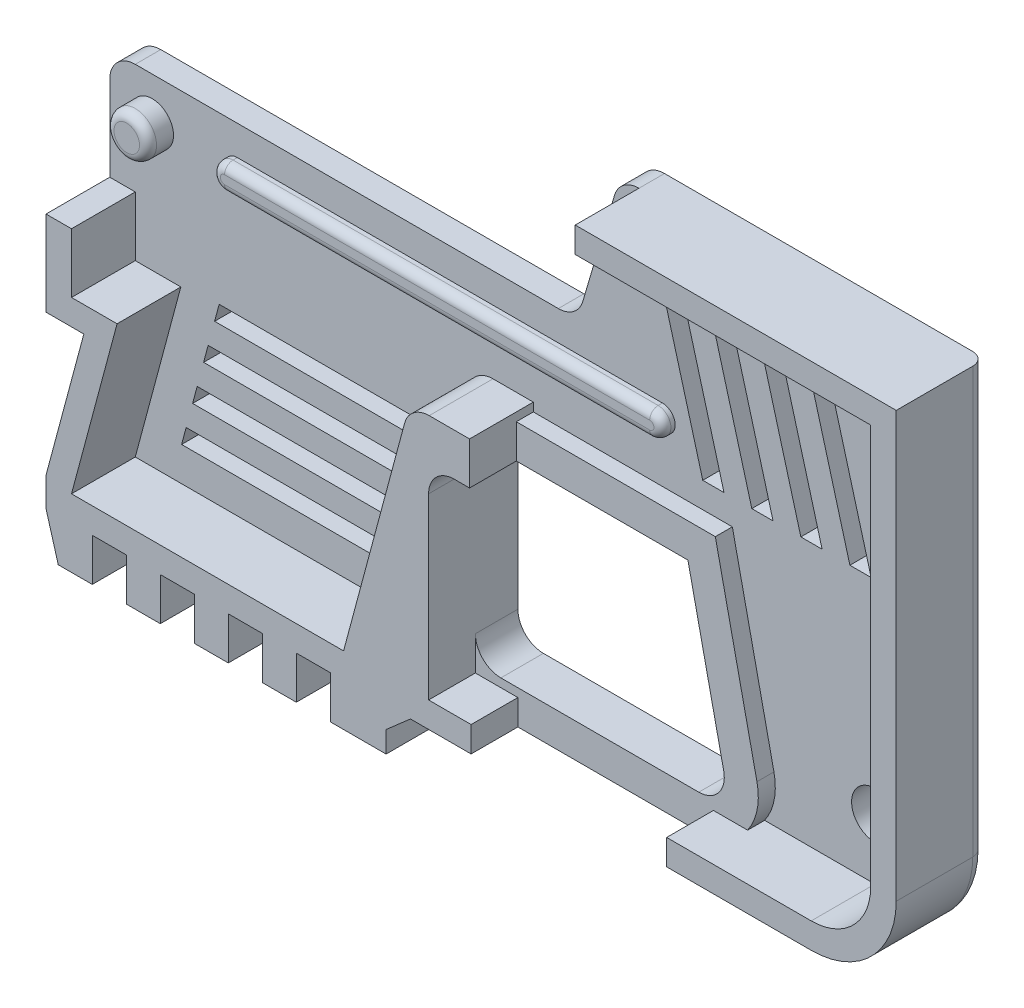
SolidWorks part; units mm, degrees
ref_plane "Front Plane" through (0, 0, 0) normal (0, 0, 1) x (1, 0, 0)
ref_plane "Top Plane" through (0, 0, 0) normal (0, 1, 0) x (1, 0, 0)
ref_plane "Right Plane" through (0, 0, 0) normal (1, 0, 0) x (0, 0, -1)
sketch "Sketch1" plane through (0, 0, 0) normal (0, 0, 1) x (1, 0, 0)
  line L0 (0.6334, 2.1535) -> (4.3666, 14.8465)
  line L1 (7.2447, 17) -> (45, 17)
  line L2 (45, 17) -> (45, -33)
  line L3 (35, -43) -> (-55, -43)
  line L4 (-55, -43) -> (-55, -3)
  line L5 (-52, 0) -> (-2.2447, 0)
  arc A0 (-55, -3) -> (-52, 0) centre (-52, -3) cw
  arc A1 (4.3666, 14.8465) -> (7.2447, 17) centre (7.2447, 14) cw
  arc A2 (0.6334, 2.1535) -> (-2.2447, 0) centre (-2.2447, 3) cw
  arc A3 (45, -33) -> (35, -43) centre (35, -33) cw
  point P9 (-55, 0)
  point P12 (5, 17)
  point P15 (0, 0)
  point P18 (45, -43)
  dimension "D6" = 3
  dimension "D7" = 3
  dimension "D8" = 10
  dimension "D1" = 100
  dimension "D2" = 60
  dimension "D3" = 17
  dimension "D4" = 40
  dimension "D5" = 55
extrude "Boss-Extrude1" add sketch "Sketch1" along normal blind 3
sketch "Sketch2" plane through (0, 0, 3) normal (0, 0, 1) x (1, 0, 0)
  line L0 (-7, -16) -> (15, -16)
  line L1 (15, -16) -> (19.2093, -35.3627)
  line L2 (16.2778, -39) -> (-7, -39)
  line L3 (-10, -36) -> (-10, -19)
  line L4 (-55, -43) -> (35, -43) construction
  line L5 (45, -33) -> (45, 17) construction
  arc A0 (19.2093, -35.3627) -> (16.2778, -39) centre (16.2778, -36) cw
  arc A1 (-7, -39) -> (-10, -36) centre (-7, -36) cw
  arc A2 (-7, -16) -> (-10, -19) centre (-7, -19) ccw
  point P8 (0, 0)
  point P11 (20, -39)
  point P14 (-10, -39)
  point P17 (-10, -16)
  dimension "D6" = 3
  dimension "D1" = 4
  dimension "D2" = 23
  dimension "D3" = 30
  dimension "D4" = 25
  dimension "D5" = 25
extrude "Cut-Extrude1" cut sketch "Sketch2" against normal through all
sketch "Sketch3" plane through (0, 0, 3) normal (0, 0, 1) x (1, 0, 0)
  line L0 (45, -33) -> (45, 17) construction
  line L1 (45, 17) -> (7.2447, 17) construction
  line L2 (45, -33) -> (45, 17)
  line L3 (45, 17) -> (7.2447, 17)
  line L4 (35, -43) -> (18, -43)
  line L5 (-55, -43) -> (35, -43) construction
  line L6 (35, -40) -> (18, -40)
  line L7 (42, -33) -> (42, 14)
  line L8 (42, 14) -> (7.2447, 14)
  line L9 (7.2447, 14) -> (7.2447, 17)
  line L10 (18, -40) -> (18, -43)
  line L11 (-5, -43) -> (-55, -43)
  line L12 (-55, -43) -> (-55, -13)
  line L13 (-55, -3) -> (-55, -43) construction
  line L14 (-55, -13) -> (-52, -13)
  line L15 (-52, -13) -> (-52, -40)
  line L16 (-52, -40) -> (-5, -40)
  line L17 (-5, -40) -> (-5, -43)
  arc A0 (35, -43) -> (45, -33) centre (35, -33) ccw construction
  arc A1 (35, -43) -> (45, -33) centre (35, -33) ccw
  arc A2 (35, -40) -> (42, -33) centre (35, -33) ccw
  dimension "D2" = 17
  dimension "D3" = 3
  dimension "D4" = 30
  dimension "D5" = 50
  dimension "D1" = 3
extrude "Boss-Extrude2" add sketch "Sketch3" along normal blind 7.5
sketch "Sketch4" plane through (0, 0, 3) normal (0, 0, 1) x (1, 0, 0)
  line L0 (15, -16) -> (-7, -16) construction
  line L1 (-10, -19) -> (-10, -36) construction
  line L2 (-7, -39) -> (16.2778, -39) construction
  line L3 (19.2093, -35.3627) -> (15, -16) construction
  line L4 (15, -16) -> (-7, -16)
  line L5 (-10, -19) -> (-10, -36)
  line L6 (-7, -39) -> (16.2778, -39)
  line L7 (19.2093, -35.3627) -> (15, -16)
  line L8 (18.2239, -12) -> (-7, -12)
  line L9 (-14, -19) -> (-14, -36)
  line L10 (-7, -43) -> (16.2778, -43)
  line L11 (23.118, -34.513) -> (18.2239, -12)
  arc A0 (-7, -16) -> (-10, -19) centre (-7, -19) ccw construction
  arc A1 (-10, -36) -> (-7, -39) centre (-7, -36) ccw construction
  arc A2 (16.2778, -39) -> (19.2093, -35.3627) centre (16.2778, -36) ccw construction
  arc A3 (-7, -16) -> (-10, -19) centre (-7, -19) ccw
  arc A4 (-10, -36) -> (-7, -39) centre (-7, -36) ccw
  arc A5 (16.2778, -39) -> (19.2093, -35.3627) centre (16.2778, -36) ccw
  arc A6 (-7, -12) -> (-14, -19) centre (-7, -19) ccw
  arc A7 (-14, -36) -> (-7, -43) centre (-7, -36) ccw
  arc A8 (16.2778, -43) -> (23.118, -34.513) centre (16.2778, -36) ccw
  dimension "D1" = 4
extrude "Boss-Extrude3" add sketch "Sketch4" along normal blind 2
sketch "Sketch5" plane through (0, 0, 3) normal (0, 0, 1) x (1, 0, 0)
  line L0 (9.2447, 11) -> (14.7447, -9)
  line L1 (14.7447, -9) -> (17.2447, -9)
  line L2 (17.2447, -9) -> (11.7447, 11)
  line L3 (11.7447, 11) -> (9.2447, 11)
  line L4 (7.2447, 14) -> (42, 14) construction
  line L5 (23.0125, -9) -> (17.5125, 11)
  line L6 (17.5125, 11) -> (15.0125, 11)
  line L7 (15.0125, 11) -> (20.5125, -9)
  line L8 (20.5125, -9) -> (23.0125, -9)
  line L9 (28.7802, -9) -> (23.2802, 11)
  line L10 (23.2802, 11) -> (20.7802, 11)
  line L11 (20.7802, 11) -> (26.2802, -9)
  line L12 (26.2802, -9) -> (28.7802, -9)
  line L13 (34.548, -9) -> (29.048, 11)
  line L14 (29.048, 11) -> (26.548, 11)
  line L15 (26.548, 11) -> (32.048, -9)
  line L16 (32.048, -9) -> (34.548, -9)
  point P6 (34.548, -9)
  dimension "D1" = 20
  dimension "D2" = 8
  dimension "D3" = 2.5
  dimension "D4" = 3
  dimension "D5" = 2
  dimension "D6" = 4
extrude "Cut-Extrude2" cut sketch "Sketch5" against normal through all
sketch "Sketch6" plane through (0, 0, 3) normal (0, 0, 1) x (1, 0, 0)
  line L0 (-52, -40) -> (-46.641, -20)
  line L1 (-46.641, -20) -> (-52, -20)
  line L2 (-52, -40) -> (-52, -13) construction
  line L3 (-52, -20) -> (-52, -40)
  dimension "D1" = 15
  dimension "D2" = 20
extrude "Boss-Extrude4" add sketch "Sketch6" along normal blind 7.5
sketch "Sketch7" plane through (0, 0, 10.5) normal (0, 0, 1) x (1, 0, 0)
  line L2 (-55, -13) -> (-55, -43) construction
  line L3 (-55, -39.605) -> (-55, -23)
  line L4 (-54.8978, -39.2235) -> (-50.5507, -23)
  line L5 (-50.5507, -23) -> (-52, -23)
  line L6 (-55, -39.605) -> (-50.5507, -23)
  line L7 (-50.5507, -23) -> (-55, -23)
  dimension "D1" = 3
extrude "Cut-Extrude3" cut sketch "Sketch7" against normal through all
sketch "Sketch8" plane through (0, 0, 3) normal (0, 0, 1) x (1, 0, 0)
  line L0 (-10, -40) -> (-10, -19)
  line L1 (-5, -40) -> (-52, -40) construction
  line L2 (-7, -16) -> (-5.1831, -16)
  line L3 (-5.1831, -16) -> (-5.1831, -11)
  line L4 (-5.1831, -11) -> (-9.9275, -11)
  line L5 (-12.8253, -13.2235) -> (-20, -40)
  line L6 (-52, -40) -> (-46.641, -20) construction
  line L7 (15, -16) -> (-7, -16) construction
  line L8 (-20, -40) -> (-10, -40)
  arc A0 (-10, -19) -> (-7, -16) centre (-7, -19) cw
  arc A1 (-9.9275, -11) -> (-12.8253, -13.2235) centre (-9.9275, -14) ccw
  point P11 (-9.9831, -40)
  dimension "D1" = 3
  dimension "D2" = 3
  dimension "D3" = 5
  dimension "D4" = 10
extrude "Boss-Extrude5" add sketch "Sketch8" along normal blind 7.5
sketch "Sketch9" plane through (0, 0, 3) normal (0, 0, 1) x (1, 0, 0)
  line L0 (-40, -5) -> (10, -5) construction
  line L1 (-40, -3.5) -> (10, -3.5)
  line L2 (-40, -6.5) -> (10, -6.5)
  line L3 (-2.2447, 0) -> (-52, 0) construction
  line L4 (-55, -3) -> (-55, -13) construction
  arc A0 (-40, -3.5) -> (-40, -6.5) centre (-40, -5) ccw
  arc A1 (10, -6.5) -> (10, -3.5) centre (10, -5) ccw
  point P2 (-15, -5)
  point P9 (-27.1224, 0)
  dimension "D1" = 3
  dimension "D2" = 50
  dimension "D3" = 5
  dimension "D4" = 15
sketch "Sketch10" plane through (0, 0, 3) normal (0, 0, 1) x (1, 0, 0)
  line L0 (-2.2447, 0) -> (-52, 0) construction
  line L1 (-55, -3) -> (-55, -13) construction
  circle A0 centre (-50, -5) radius 2.5
  dimension "D3" = 5
  dimension "D1" = 5
  dimension "D2" = 5
extrude "Boss-Extrude6" add sketch "Sketch10" along normal blind 3
fillet "Fillet2" radius 1 1 edges at (-47.5, -5, 6)
sketch "Sketch11" plane through (0, 0, 3) normal (0, 0, 1) x (1, 0, 0)
  circle A0 centre (35, -33) radius 2.75
  dimension "D1" = 5.5
extrude "Cut-Extrude5" cut sketch "Sketch11" against normal through all
fillet "Fillet3" radius 1.5 3 edges at (-10, -43, 0) (42.0711, -40.0711, 0) (45, -8, 0)
sketch "Sketch12" plane through (0, 0, 3) normal (0, 0, 1) x (1, 0, 0)
  line L0 (-46.5517, -36) -> (-22.5517, -36)
  line L1 (-22.5517, -36) -> (-22.0158, -34)
  line L2 (-22.0158, -34) -> (-46.0158, -34)
  line L3 (-46.0158, -34) -> (-46.5517, -36)
  line L4 (-52, -40) -> (-46.641, -20) construction
  line L5 (-12.8253, -13.2235) -> (-20, -40) construction
  line L6 (-20, -40) -> (-52, -40) construction
  line L7 (-45.2576, -31.1704) -> (-21.2576, -31.1704)
  line L8 (-21.2576, -31.1704) -> (-20.7217, -29.1704)
  line L9 (-20.7217, -29.1704) -> (-44.7217, -29.1704)
  line L10 (-44.7217, -29.1704) -> (-45.2576, -31.1704)
  line L11 (-43.9635, -26.3407) -> (-19.9635, -26.3407)
  line L12 (-19.9635, -26.3407) -> (-19.4276, -24.3407)
  line L13 (-19.4276, -24.3407) -> (-43.4276, -24.3407)
  line L14 (-43.4276, -24.3407) -> (-43.9635, -26.3407)
  line L15 (-42.6694, -21.5111) -> (-18.6694, -21.5111)
  line L16 (-18.6694, -21.5111) -> (-18.1335, -19.5111)
  line L17 (-18.1335, -19.5111) -> (-42.1335, -19.5111)
  line L18 (-42.1335, -19.5111) -> (-42.6694, -21.5111)
  dimension "D1" = 2
  dimension "D2" = 24
  dimension "D3" = 3.5
  dimension "D4" = 4
  dimension "D5" = 4
extrude "Cut-Extrude6" cut sketch "Sketch12" against normal through all
sketch "Sketch13" plane through (0, 0, 0) normal (0, 0, 1) x (1, 0, 0)
  line L0 (-55, -43) -> (-53.5586, -48.0092)
  line L1 (-53.5586, -48.0092) -> (-14.9974, -48.0092)
  line L2 (-14.9974, -48.0092) -> (-14.9974, -45.5046)
  line L3 (-14.9974, -45.5046) -> (-12.1335, -43)
  line L4 (-55, -43) -> (-5, -43) construction
  line L5 (-12.1335, -43) -> (-55, -43)
extrude "Boss-Extrude7" add sketch "Sketch13" along normal blind 10.5
chamfer "Chamfer1" distance 1 angle 45 2 edges at (-33.5667, -43, 0) (-34.278, -48.0092, 0)
sketch "Sketch14" plane through (0, 0, 10.5) normal (0, 0, 1) x (1, 0, 0)
  line L0 (-53.5586, -48.0092) -> (-14.9974, -48.0092) construction
  line L1 (-49.5586, -48.0092) -> (-45.5586, -48.0092)
  line L2 (-49.5586, -48.0092) -> (-49.5586, -43)
  line L3 (-49.5586, -43) -> (-45.5586, -43)
  line L4 (-45.5586, -48.0092) -> (-45.5586, -43)
  line L5 (-20, -40) -> (-52, -40) construction
  line L6 (-41.5586, -43) -> (-37.5586, -43)
  line L7 (-37.5586, -48.0092) -> (-37.5586, -43)
  line L8 (-41.5586, -48.0092) -> (-37.5586, -48.0092)
  line L9 (-41.5586, -48.0092) -> (-41.5586, -43)
  line L10 (-33.5586, -43) -> (-29.5586, -43)
  line L11 (-29.5586, -48.0092) -> (-29.5586, -43)
  line L12 (-33.5586, -48.0092) -> (-29.5586, -48.0092)
  line L13 (-33.5586, -48.0092) -> (-33.5586, -43)
  line L14 (-25.5586, -43) -> (-21.5586, -43)
  line L15 (-21.5586, -48.0092) -> (-21.5586, -43)
  line L16 (-25.5586, -48.0092) -> (-21.5586, -48.0092)
  line L17 (-25.5586, -48.0092) -> (-25.5586, -43)
  dimension "D1" = 4
  dimension "D2" = 4
  dimension "D3" = 3
  dimension "D4" = 4
extrude "Cut-Extrude7" cut sketch "Sketch14" against normal through all
extrude "Boss-Extrude8" add sketch "Sketch9" along normal blind 1.5
fillet "Fillet4" radius 1 4 edges at (-15, -3.5, 4.5) (11.5, -5, 4.5) (-15, -6.5, 4.5) (-41.5, -5, 4.5)
